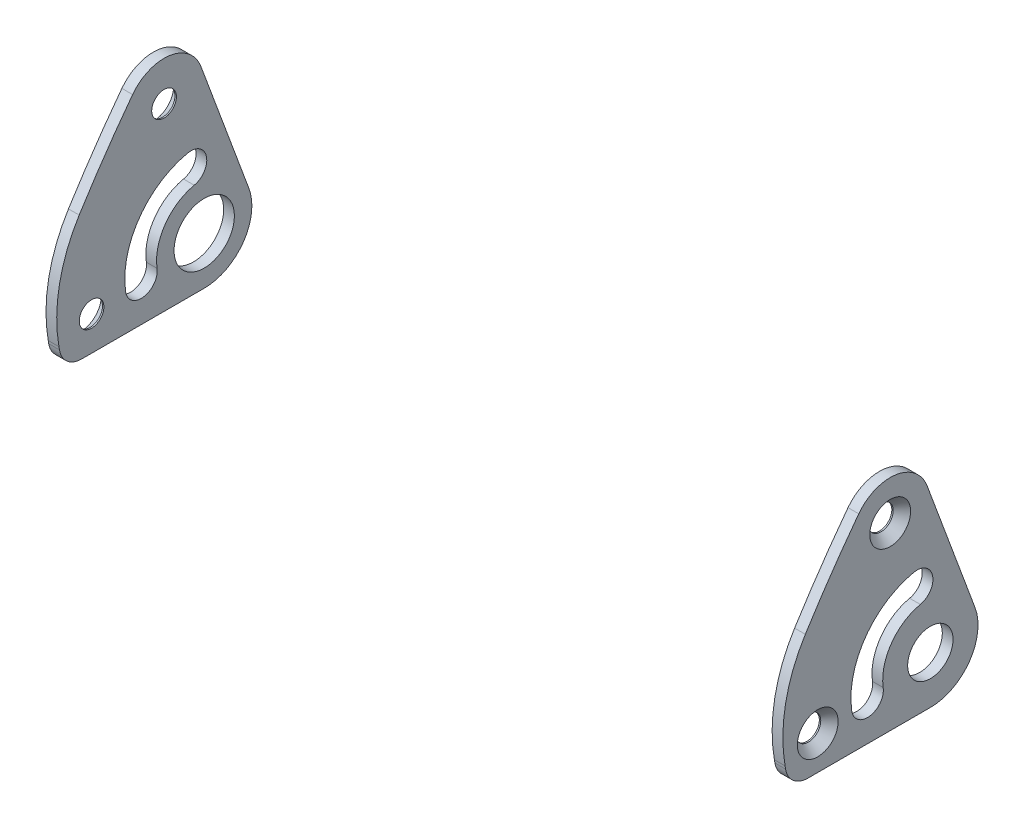
SolidWorks part; units mm, degrees
material "Ti-6Al-4VSolution treated and aged (SS)"
ref_plane "Front Plane" through (0, 0, 0) normal (0, 0, 1) x (1, 0, 0)
ref_plane "Top Plane" through (0, 0, 0) normal (0, 1, 0) x (1, 0, 0)
ref_plane "Right Plane" through (0, 0, 0) normal (1, 0, 0) x (0, 0, -1)
sketch "Sketch1" plane through (50.05, 0, 0) normal (1, 0, 0) x (0, 0, -1)
  line L1 (-163.3043, 20.32) -> (-154.1497, 20.32) construction
  line L2 (-171.4659, 20.32) -> (-151.65, 20.32)
  line L4 (-171.4659, 20.32) -> (-171.9734, 23.4009)
  line L6 (-145.3974, 29.3029) -> (-155.4683, 56.4984)
  arc A1 (-169.1435, 37.9367) -> (-155.4683, 56.4984) centre (-39.9608, -42.9187) cw
  circle A2 centre (-151.65, 26.9875) radius 4.2227
  arc A4 (-140.0779, 71.9827) -> (-169.1435, 37.9367) centre (-39.9608, -42.9187) ccw construction
  arc A6 (-171.97, -24.13) -> (-171.9734, 23.4009) centre (-306.6951, -0.3743) ccw construction
  arc A7 (-151.65, 20.32) -> (-145.3974, 29.3029) centre (-151.65, 26.9875) ccw
  arc A9 (-169.1435, 37.9367) -> (-171.9734, 23.4009) centre (-151.65, 26.9875) ccw construction
  arc A10 (-169.1435, 37.9367) -> (-171.9734, 23.4009) centre (-151.65, 26.9875) ccw
  arc A12 (-152.0988, 47.3993) -> (-161.6694, 48.8025) centre (-157.2676, 45.4853) ccw
  dimension "D1" = 8.4455
  dimension "D2" = 5.5118
  dimension "D3" = 69.68
extrude "Boss-Extrude1" add sketch "Sketch1" along normal blind 1.5 contours L6 A12 A1 L2 A7 A2 region at (50.05, 33.6096, 159.4667)
sketch "Sketch2" plane through (51.55, 0, 0) normal (1, 0, 0) x (0, 0, -1)
  line L4 (-161.5796, 23.495) -> (-166.5679, 23.495) construction
  line L6 (-151.3256, 36.1685) -> (-153.5891, 42.2809) construction
  line L9 (-145.3974, 29.3029) -> (-152.0988, 47.3993) construction
  line L10 (-171.4659, 20.32) -> (-151.65, 20.32) construction
  arc A9 (-151.65, 20.32) -> (-145.3974, 29.3029) centre (-151.65, 26.9875) ccw construction
  arc A12 (-153.0484, 33.5067) -> (-158.2491, 26.035) centre (-151.65, 26.9875) ccw
  arc A16 (-153.9807, 37.8528) -> (-162.6485, 25.4) centre (-151.65, 26.9875) ccw
  arc A18 (-153.0484, 33.5067) -> (-153.9807, 37.8528) centre (-153.5146, 35.6798) ccw
  arc A19 (-158.2491, 26.035) -> (-162.6485, 25.4) centre (-160.4488, 25.7175) cw
  dimension "D1" = 3.175
  dimension "D2" = 3.175
  dimension "D3" = 11.1125
extrude "Cut-Extrude1" cut sketch "Sketch2" against normal up to next and the other way through all contours L6 A16 L4 A12 region at (51.55, 31.4145, 158.0102)
fillet "Fillet3" radius 3.175 1 edges at (50.8, 20.32, 171.4659)
hole_wizard "CSK for #4 Flat Head Machine Screw1" positions "Sketch4" profile "Sketch6" countersink size "#4" standard "ANSI Inch" end condition up to next
sketch "Sketch4" plane through (51.55, 0, 0) normal (1, 0, 0) x (0, 0, -1)
  line L0 (-168.7712, 20.32) -> (-151.65, 20.32) construction
  arc A0 (-152.0988, 47.3993) -> (-161.6694, 48.8025) centre (-157.2676, 45.4853) ccw construction
  circle A1 centre (-167.4103, 25.0825) radius 4.7625 construction
  arc A4 (-153.9807, 37.8528) -> (-162.6485, 25.4) centre (-151.65, 26.9875) ccw construction
  point P0 (-167.4103, 25.0825)
  point P3 (-157.2676, 45.4853)
sketch "Sketch6" plane through (51.55, 25.0825, 167.4103) normal (0, 1, 0) x (0, 0, -1)
  line L0 (0, 0) -> (0, 1.5)
  line L1 (0, 1.5) -> (1.7272, 1.5)
  line L2 (1.7272, 1.5) -> (1.7272, 1.3003)
  line L3 (1.7272, 1.3003) -> (2.8575, 0)
  line L5 (2.8575, 0) -> (0, 0)
  line L6 (-1.7272, 1.3003) -> (-2.8575, 0) construction
  line L11 (0, -6.35) -> (0, 107.95) construction
  dimension "Thru Hole Dia." = 3.4544
  dimension "Thru Hole Depth" = 1.5
  dimension "Near C'Sink Dia." = 5.715
  dimension "Near C'Sink Angle" = 82
mirror "Mirror2" about plane through (0, 0, 0) normal (1, 0, 0) of bodies 110 101
sketch "Sketch7" plane through (51.55, 0, 0) normal (1, 0, 0) x (0, 0, -1)
  circle A0 centre (-151.65, 26.9875) radius 4.2227 construction
  circle A1 centre (-151.65, 26.9875) radius 4.2227
  circle A2 centre (-151.65, 26.9875) radius 3.175
  dimension "D1" = 6.35
extrude "Boss-Extrude2" add sketch "Sketch7" against normal up to surface (1.5 mm away) up to face at (50.05, 25.0825, 165.6831)
equation "\"weapon shaft threads\"= 5 / 16"
equation "\"D1@Sketch1\"=\"weapon shaft threads\" + .02in"
equation "\"D1@Boss-Extrude1\"=1.5mm"
